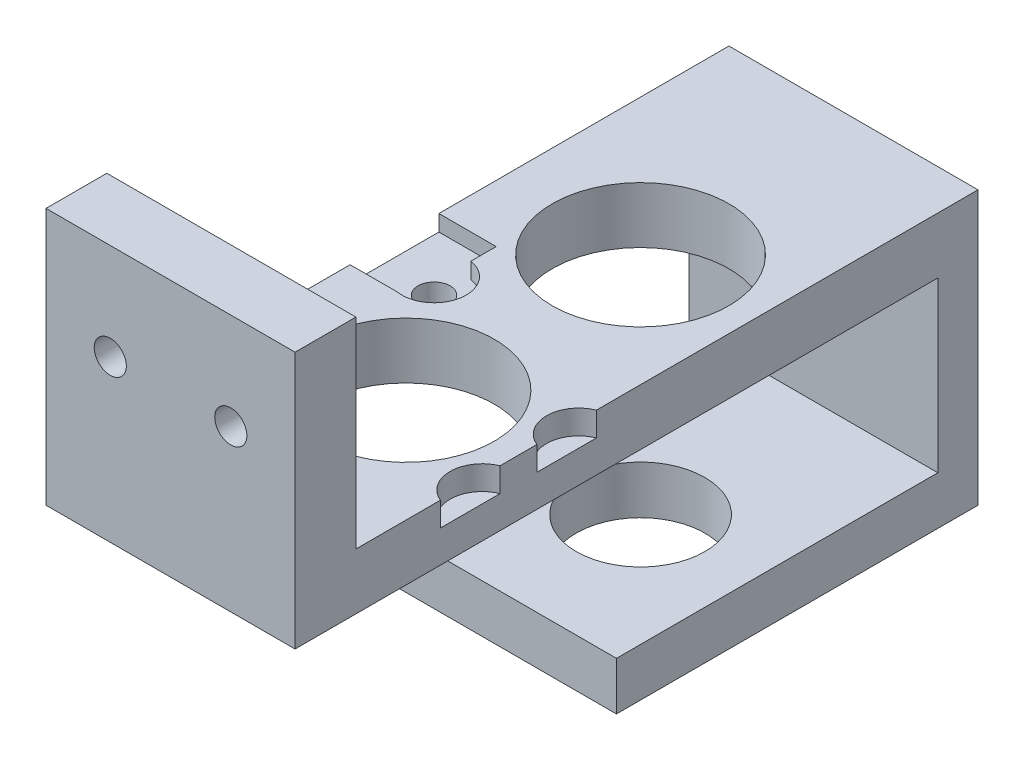
SolidWorks part; units mm, degrees
ref_plane "Front Plane" through (0, 0, 0) normal (0, 0, 1) x (1, 0, 0)
ref_plane "Top Plane" through (0, 0, 0) normal (0, 1, 0) x (1, 0, 0)
ref_plane "Right Plane" through (0, 0, 0) normal (1, 0, 0) x (0, 0, -1)
sketch "Sketch1" plane through (0, 0, 0) normal (0, 1, 0) x (1, 0, 0)
  line L1 (-50.1619, 28.7652) -> (-19.1619, 28.7652)
  line L2 (-50.1619, 28.7652) -> (-50.1619, -56.2348)
  line L3 (-50.1619, -56.2348) -> (-19.1619, -56.2348)
  line L4 (-19.1619, 28.7652) -> (-19.1619, -56.2348)
  dimension "D1" = 85
  dimension "D2" = 31
extrude "Boss-Extrude1" add sketch "Sketch1" along normal blind 7
sketch "Sketch2" plane through (0, 7, 0) normal (0, 1, 0) x (1, 0, 0)
  line L0 (-50.1619, -56.2348) -> (-19.1619, -56.2348) construction
  line L1 (-50.1619, 28.7652) -> (-50.1619, -56.2348) construction
  circle A0 centre (-33.1619, 0.7652) radius 11
  dimension "D1" = 22
  dimension "D2" = 57
  dimension "D3" = 17
extrude "Cut-Extrude1" cut sketch "Sketch2" against normal blind 100
sketch "Sketch3" plane through (0, 7, 0) normal (0, 1, 0) x (1, 0, 0)
  line L0 (-50.1619, 28.7652) -> (-50.1619, -56.2348) construction
  circle A0 centre (-33.1619, -28.4348) radius 11
  circle A1 centre (-33.1619, 0.7652) radius 11 construction
  dimension "D1" = 22
  dimension "D2" = 29.2
  dimension "D3" = 17
extrude "Cut-Extrude2" cut sketch "Sketch3" against normal blind 7
sketch "Sketch4" plane through (0, 7, 0) normal (0, 1, 0) x (1, 0, 0)
  line L0 (-19.1619, -56.2348) -> (-19.1619, 28.7652) construction
  line L1 (-50.1619, -56.2348) -> (-19.1619, -56.2348)
  line L2 (-50.1619, -56.2348) -> (-50.1619, -48.6648)
  line L3 (-50.1619, -48.6648) -> (-19.1619, -48.6648)
  line L4 (-19.1619, -56.2348) -> (-19.1619, -48.6648)
  dimension "D1" = 7.57
extrude "Boss-Extrude3" add sketch "Sketch4" along normal blind 25
sketch "Sketch5" plane through (0, 0, 48.6648) normal (0, 0, -1) x (-1, 0, 0)
  line L0 (50.1619, 32) -> (50.1619, 7) construction
  line L1 (19.1619, 32) -> (50.1619, 32) construction
  circle A0 centre (42.1619, 20) radius 2
  circle A1 centre (27.1619, 20) radius 2
  dimension "D1" = 4
  dimension "D2" = 4
  dimension "D3" = 8
  dimension "D4" = 15
  dimension "D5" = 0
  dimension "D6" = 12
extrude "Cut-Extrude3" cut sketch "Sketch5" against normal blind 14
sketch "Sketch6" plane through (0, 7, 0) normal (0, 1, 0) x (1, 0, 0)
  circle A0 centre (-43.6619, -14.4348) radius 2
  circle A1 centre (-43.6619, -42.4348) radius 2
  circle A2 centre (-33.1619, -28.4348) radius 11 construction
  dimension "D1" = 4
  dimension "D2" = 4
  dimension "D3" = 28
  dimension "D4" = 10.5
  dimension "D5" = 14
  dimension "D6" = 0
extrude "Cut-Extrude4" cut sketch "Sketch6" against normal blind 14
sketch "Sketch9" plane through (0, 7, 0) normal (0, 1, 0) x (1, 0, 0)
  circle A2 centre (-33.1619, 0.7652) radius 8
  circle A3 centre (-33.1619, 0.7652) radius 11 construction
  dimension "D1" = 16
  dimension "D2" = 0
sketch "Sketch10" plane through (0, 0, 0) normal (0, -1, 0) x (1, 0, 0)
  line L0 (-19.1619, 56.2348) -> (-19.1619, -28.7652) construction
  line L1 (-50.1619, -28.7652) -> (-19.1619, -28.7652)
  line L2 (-50.1619, -28.7652) -> (-50.1619, -23.7652)
  line L3 (-50.1619, -23.7652) -> (-19.1619, -23.7652)
  line L4 (-19.1619, -28.7652) -> (-19.1619, -23.7652)
  dimension "D1" = 5
extrude "Boss-Extrude4" add sketch "Sketch10" along normal blind 27
sketch "Sketch11" plane through (0, 0, -23.7652) normal (0, 0, 1) x (1, 0, 0)
  line L0 (-19.1619, -27) -> (-19.1619, 0) construction
  line L1 (-50.1619, -27) -> (-19.1619, -27)
  line L2 (-50.1619, -27) -> (-50.1619, -21)
  line L3 (-50.1619, -21) -> (-19.1619, -21)
  line L4 (-19.1619, -27) -> (-19.1619, -21)
  dimension "D1" = 6
extrude "Boss-Extrude5" add sketch "Sketch11" along normal blind 40
extrude "Cut-Extrude5" cut sketch "Sketch9" against normal blind 40
sketch "Sketch13" plane through (0, 7, 0) normal (0, 1, 0) x (1, 0, 0)
  circle A0 centre (-43.6619, -14.4348) radius 4
  circle A2 centre (-43.6619, -14.4348) radius 2 construction
  circle A3 centre (-43.6619, -42.4348) radius 4
  circle A4 centre (-43.6619, -42.4348) radius 2 construction
  circle A5 centre (-43.6619, -42.4348) radius 2 construction
  dimension "D1" = 0
  dimension "D2" = 8
  dimension "D3" = 0
  dimension "D4" = 0
  dimension "D5" = 8
extrude "Cut-Extrude6" cut sketch "Sketch13" against normal blind 2
sketch "Sketch15" plane through (0, 7, 0) normal (0, 1, 0) x (1, 0, 0)
  line L0 (-50.1619, 28.7652) -> (-50.1619, -48.6648) construction
  line L3 (-50.1619, -7.3373) -> (-43.0297, -7.3373)
  line L6 (-50.1619, -7.3373) -> (-50.1619, -18.3845)
  line L7 (-50.1619, -18.3845) -> (-43.0297, -18.3845)
  line L8 (-43.0297, -7.3373) -> (-43.0297, -18.3845)
  line L9 (-19.1619, -48.6648) -> (-50.1619, -48.6648) construction
  line L10 (-50.1619, -39.308) -> (-42.4267, -39.308)
  line L11 (-50.1619, -39.308) -> (-50.1619, -48.6648)
  line L12 (-50.1619, -48.6648) -> (-42.4267, -48.6648)
  line L13 (-42.4267, -39.308) -> (-42.4267, -48.6648)
  circle A4 centre (-43.6619, -14.4348) radius 4 construction
extrude "Cut-Extrude9" cut sketch "Sketch15" against normal blind 2
sketch "Sketch17" plane through (0, 7, 0) normal (0, 1, 0) x (1, 0, 0)
  line L0 (-17.6619, -22.4348) -> (-17.6619, -34.4348)
  line L1 (-17.6619, -28.4348) -> (-10.263, -28.4348)
  circle A0 centre (-17.6619, -22.4348) radius 4
  circle A1 centre (-17.6619, -34.4348) radius 4
  point P6 (0, 0)
  point P8 (-33.1619, -28.4348)
  line M12 (-19.1619, -48.6648) -> (-19.1619, 28.7652)
  dimension "D1" = 8
  dimension "D2" = 8
  dimension "D3" = 12
  dimension "D4" = 0
  dimension "D5" = 15.5
extrude "Cut-Extrude10" cut sketch "Sketch17" against normal blind 3 contours A0 M12 | A1 M12 region at (-20.1948, 7, 22.4348) region at (-20.1948, 7, 34.4348)
